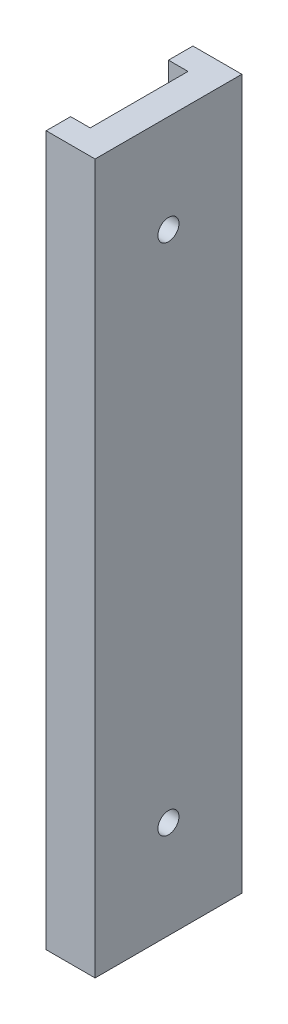
SolidWorks part; units mm, degrees
ref_plane "Front Plane" through (0, 0, 0) normal (0, 0, 1) x (1, 0, 0)
ref_plane "Top Plane" through (0, 0, 0) normal (0, 1, 0) x (1, 0, 0)
ref_plane "Right Plane" through (0, 0, 0) normal (1, 0, 0) x (0, 0, -1)
ref_plane "Plane1" through (0, 260, 0) normal (0, -1, 0) x (-1, 0, 0)
sketch "Sketch1" plane through (0, 260, 0) normal (0, -1, 0) x (-1, 0, 0)
  line L0 (71.5, -127.5) -> (61.5, -127.5)
  line L1 (61.5, -127.5) -> (61.5, -97.5)
  line L2 (61.5, -97.5) -> (71.5, -97.5)
  line L3 (71.5, -97.5) -> (71.5, -102.5)
  line L4 (71.5, -102.5) -> (67.5, -102.5)
  line L5 (67.5, -102.5) -> (67.5, -122.5)
  line L6 (67.5, -122.5) -> (71.5, -122.5)
  line L7 (71.5, -122.5) -> (71.5, -127.5)
  line L8 (68.9986, -122.5) -> (74.3631, -122.5) construction
  line L9 (68.9986, -102.5) -> (74.3631, -102.5) construction
  line L10 (67.5, -115.6369) -> (67.5, -121.0014) construction
  point P6 (0, 0)
  point P13 (0, 0)
  point P14 (0, 0)
  point P15 (0, 0)
  point P16 (0, 0)
  point P19 (73.2648, -127.5)
  dimension "D1" = 5
  dimension "D2" = 10
  dimension "D3" = 6
extrude "Boss-Extrude1" add sketch "Sketch1" along normal blind 145
hole_wizard "M4 Clearance Hole1" positions "Sketch2" profile "Sketch4" hole size "M4" standard "ISO" end condition through all
sketch "Sketch2" plane through (-61.5, 0, 0) normal (1, 0, 0) x (0, 0, -1)
  line L0 (-112.5, 240) -> (-112.5, 135) construction
  line L2 (-97.5, 260) -> (-127.5, 260) construction
  line L3 (-97.5, 115) -> (-127.5, 115) construction
  point P1 (-112.5, 240)
  point P2 (-112.5, 135)
  point P7 (-112.5, 260)
  dimension "D1" = 20
  dimension "D2" = 20
sketch "Sketch4" plane through (-61.5, 240, 112.5) normal (0, 1, 0) x (0, 0, -1)
  line L0 (0, 0) -> (0, 10)
  line L1 (0, 10) -> (2.15, 10)
  line L2 (2.15, 10) -> (2.15, 0)
  line L5 (2.15, 0) -> (0, 0)
  line L11 (0, -6.35) -> (0, 107.95) construction
  dimension "Thru Hole Dia." = 4.3
  dimension "Thru Hole Depth" = 10
